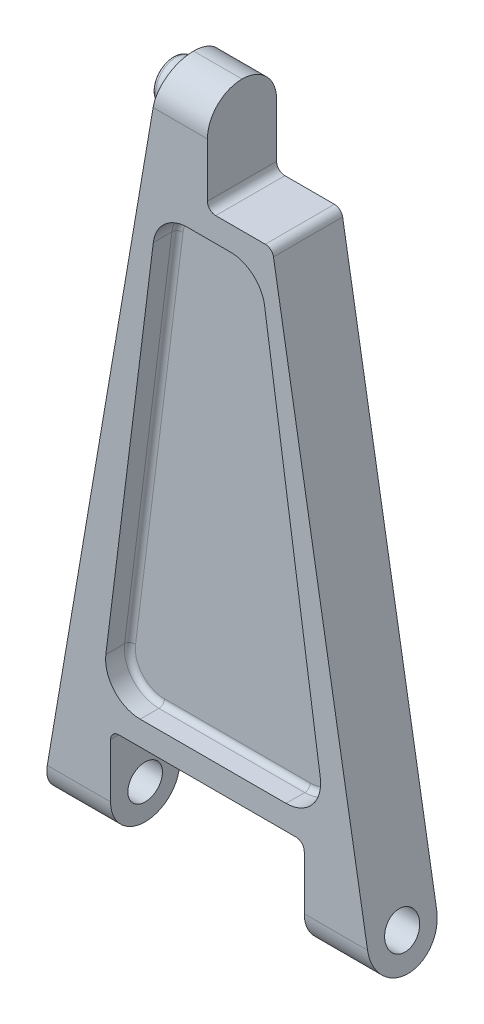
SolidWorks part; units mm, degrees
ref_plane "Front Plane" through (0, 0, 0) normal (0, 0, 1) x (1, 0, 0)
ref_plane "Top Plane" through (0, 0, 0) normal (0, 1, 0) x (1, 0, 0)
ref_plane "Right Plane" through (0, 0, 0) normal (1, 0, 0) x (0, 0, -1)
sketch "Sketch1" plane through (0, 0, 0) normal (0, 0, 1) x (1, 0, 0)
  line L0 (0, 0) -> (0, 1500) construction
  line L1 (-240, 0) -> (240, 0)
  line L2 (-70, 1000) -> (70, 1000)
  line L3 (-70, 1000) -> (-240, 0)
  line L4 (70, 1000) -> (240, 0)
  dimension "D1" = 240
  dimension "D3" = 1000
  dimension "D4" = 1500
  dimension "D6" = 70
extrude "Boss-Extrude1" add sketch "Sketch1" along normal mid plane 100
fillet "Fillet1" radius 50 4 edges at (0, 1000, 50) (0, 1000, -50) (0, 0, 50) (0, 0, -50)
sketch "Sketch4" plane through (0, 0, 0) normal (0, 0, 1) x (1, 0, 0)
  line L1 (-140, 0) -> (140, 0)
  line L2 (-140, 0) -> (-140, 140)
  line L3 (-140, 140) -> (140, 140)
  line L4 (140, 0) -> (140, 140)
  line L5 (70, 1000) -> (-70, 1000) construction
  line L6 (0, 1000) -> (94, 1000)
  line L7 (0, 1000) -> (0, 860)
  line L8 (0, 860) -> (94, 860)
  line L9 (94, 1000) -> (94, 860)
  dimension "D1" = 280
  dimension "D2" = 140
  dimension "D3" = 140
  dimension "D4" = 94
  dimension "D5" = 140
extrude "Cut-Extrude2" cut sketch "Sketch4" against normal through all both and the other way through all
sketch "Sketch5" plane through (0, 0, 0) normal (1, 0, 0) x (0, 0, -1)
  line L6 (-50, 950) -> (-50, 860)
  line L7 (-50, 860) -> (50, 860)
  line L8 (50, 860) -> (50, 950)
  circle A0 centre (0, 950) radius 30
  arc A5 (50, 950) -> (0, 1000) centre (0, 950) ccw
  arc A6 (0, 1000) -> (-50, 950) centre (0, 950) ccw
  arc A7 (50, 950) -> (0, 1000) centre (0, 950) ccw
  arc A8 (0, 1000) -> (-50, 950) centre (0, 950) ccw
  dimension "D1" = 60
  dimension "D2" = 0
extrude "Boss-Extrude2" add sketch "Sketch5" against normal blind 100 contours A0 region at (0, 950, 0)
fillet "Fillet2" radius 5 1 edges at (-100, 950, -30)
fillet "Fillet3" radius 12 4 edges at (140, 140, 0) (-140, 140, 0) (0, 860, 0) (93.8, 860, 0)
sketch "Sketch6" plane through (0, 0, 50) normal (0, 0, 1) x (1, 0, 0)
  line L0 (76.4413, 825) -> (-72.7573, 825)
  line L1 (-153.8117, 175) -> (171.4751, 175)
  line L2 (171.4751, 175) -> (76.4413, 825)
  line L3 (-72.7573, 825) -> (-153.8117, 175)
  line L4 (12, 860) -> (83.6678, 860) construction
  line L5 (128, 140) -> (-128, 140) construction
  line L6 (-78.5, 950) -> (-231.5, 50) construction
  line L7 (231.5, 50) -> (95.4981, 850.0111) construction
  dimension "D1" = 35
  dimension "D2" = 35
  dimension "D3" = 2.54
  dimension "D4" = 1.33
  dimension "D5" = 55.64
extrude "Cut-Extrude4" cut sketch "Sketch6" against normal blind 35
fillet "Fillet4" radius 50 4 edges at (171.4751, 175, 32.5) (-153.8117, 175, 32.5) (76.4413, 825, 32.5) (-72.7573, 825, 32.5)
fillet "Fillet5" radius 8 8 edges at (-134.6685, 191.9043, 15) (-112.513, 506.187, 15) (-61.7007, 812.479, 15) (2.3075, 825, 15) (65.9181, 812.8264, 15) (122.9006, 507.2334, 15) (151.4596, 192.3019, 15) (8.2219, 175, 15)
mirror "Mirror1" about plane through (0, 0, 0) normal (0, 0, 1) of "Cut-Extrude4", "Fillet5", "Fillet4"
sketch "Sketch7" plane through (0, 0, 0) normal (1, 0, 0) x (0, 0, -1)
  circle A0 centre (0, 50) radius 25
  dimension "D1" = 50
extrude "Cut-Extrude5" cut sketch "Sketch7" against normal mid plane 500
